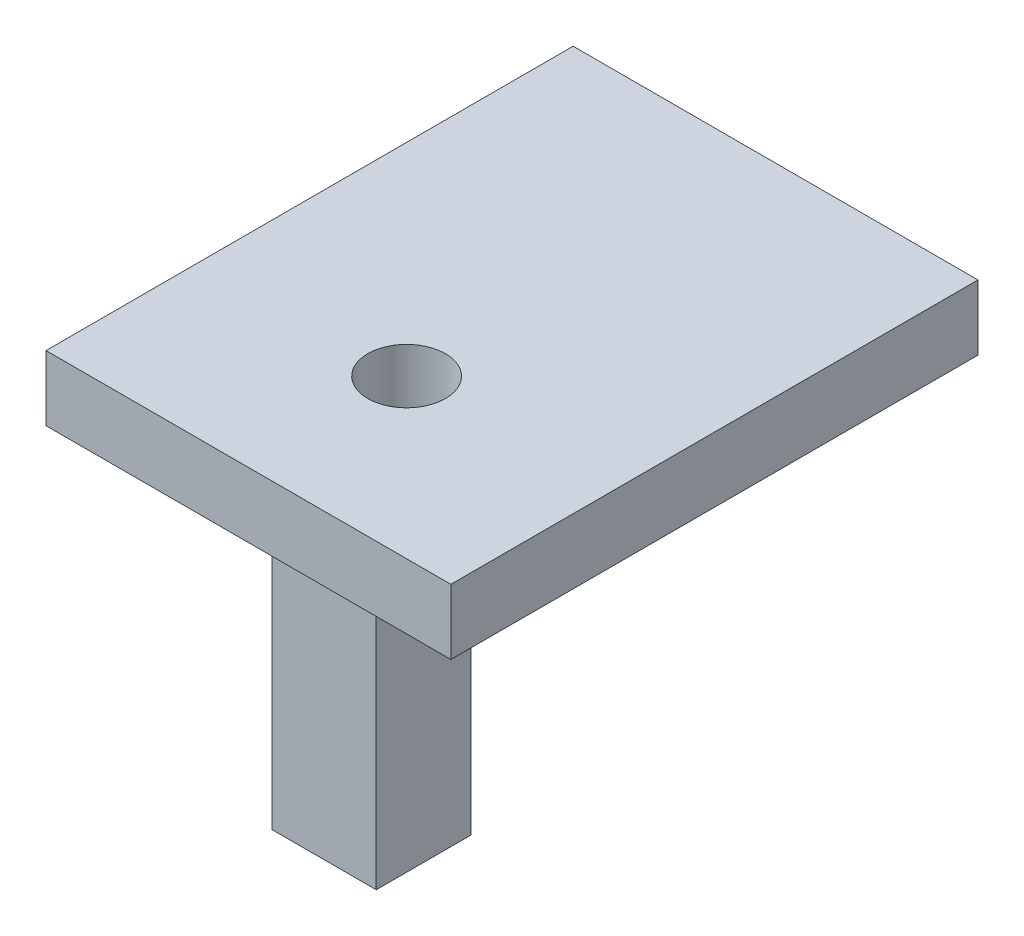
SolidWorks part; units mm, degrees
ref_plane "Front Plane" through (0, 0, 0) normal (0, 0, 1) x (1, 0, 0)
ref_plane "Top Plane" through (0, 0, 0) normal (0, 1, 0) x (1, 0, 0)
ref_plane "Right Plane" through (0, 0, 0) normal (1, 0, 0) x (0, 0, -1)
sketch "Sketch1" plane through (0, 0, 0) normal (0, 1, 0) x (1, 0, 0)
  line L1 (-31.1, 40.4921) -> (31.1, 40.4921)
  line L2 (-31.1, 40.4921) -> (-31.1, -40.4921)
  line L3 (-31.1, -40.4921) -> (31.1, -40.4921)
  line L4 (31.1, 40.4921) -> (31.1, -40.4921)
  line L5 (-31.1, 40.4921) -> (31.1, -40.4921) construction
  line L6 (-31.1, -40.4921) -> (31.1, 40.4921) construction
  point P0 (0, 0)
  dimension "D1" = 62.2
  dimension "D2" = 80.9841
extrude "Boss-Extrude1" add sketch "Sketch1" along normal blind 10
sketch "Sketch2" plane through (0, 10, 0) normal (0, 1, 0) x (1, 0, 0)
  line L0 (-31.1, -40.4921) -> (31.1, -40.4921) construction
  circle A0 centre (0, -16.1921) radius 5.969
  dimension "D1" = 24.3
extrude "Cut-Extrude1" cut sketch "Sketch2" against normal blind 10
sketch "Sketch3" plane through (0, 0, 0) normal (0, -1, 0) x (1, 0, 0)
  line L0 (31.1, -40.4921) -> (-31.1, -40.4921) construction
  line L1 (-15.1, -8.7921) -> (-31.1, -8.7921)
  line L2 (-15.1, -8.7921) -> (-15.1, 5.7606)
  line L3 (-15.1, 5.7606) -> (-31.1, 5.7606)
  line L4 (-31.1, -8.7921) -> (-31.1, 5.7606)
  line L5 (-31.1, -40.4921) -> (-31.1, 40.4921) construction
  dimension "D1" = 16
  dimension "D2" = 31.7
  dimension "D3" = 14.5526
  dimension "D4" = 0
extrude "Boss-Extrude2" add sketch "Sketch3" along normal blind 71.11
